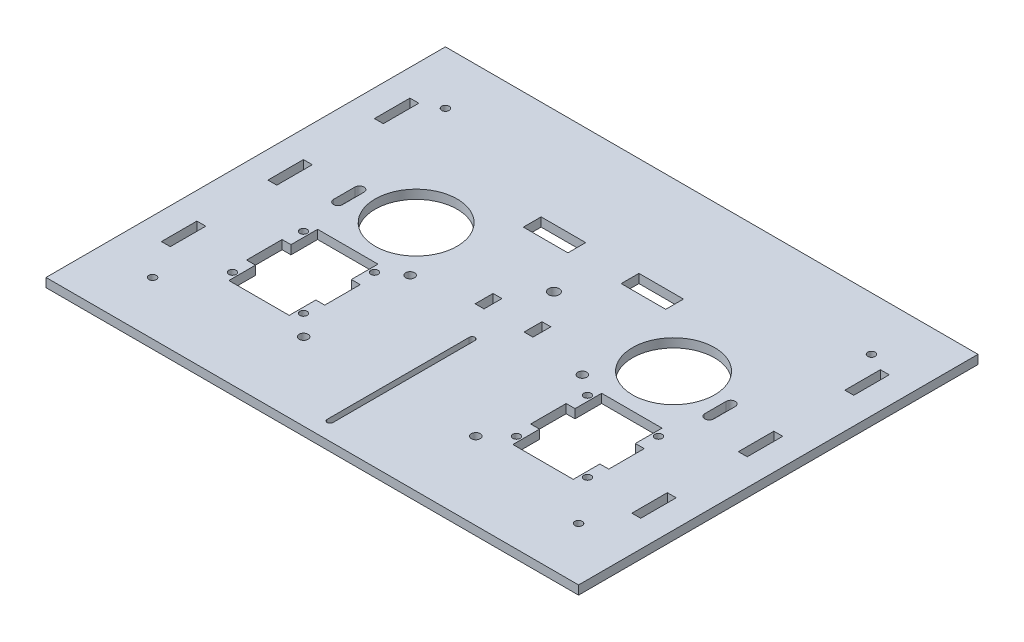
SolidWorks part; units mm, degrees
ref_plane "前基準面" through (0, 0, 0) normal (0, 0, 1) x (1, 0, 0)
ref_plane "上基準面" through (0, 0, 0) normal (0, 1, 0) x (1, 0, 0)
ref_plane "右基準面" through (0, 0, 0) normal (1, 0, 0) x (0, 0, -1)
sketch "草圖1" plane through (0, 0, 0) normal (0, 1, 0) x (1, 0, 0)
  line L0 (-130, 90) -> (130, 90) construction
  line L1 (-150, 100) -> (150, 100) construction
  line L2 (-150, 100) -> (-150, -100)
  line L3 (-150, -100) -> (150, -100) construction
  line L5 (0, 100) -> (0, -100) construction
  line L8 (-130, 100) -> (-110, 100) construction
  line L9 (-150, 100) -> (-150, -100) construction
  line L16 (-130, 100) -> (-130, -100) construction
  line L17 (-130, -100) -> (-110, -100) construction
  line L20 (-150, -100) -> (-150, -120)
  line L23 (-150, -100) -> (150, -100) construction
  line L35 (-110, 100) -> (-110, -100) construction
  line L38 (-110, 100) -> (110, 100) construction
  line L41 (-110, 100) -> (-110, 80) construction
  line L50 (-110, 80) -> (110, 80) construction
  line L59 (110, 100) -> (110, 80) construction
  line L65 (-150, -100) -> (150, -100) construction
  line L68 (150, -100) -> (150, 100)
  line L70 (-150, 100) -> (150, 100) construction
  line L73 (-150, 100) -> (-150, 105)
  line L77 (110, 100) -> (130, 100) construction
  line L80 (110, 100) -> (110, -100) construction
  line L83 (110, -100) -> (130, -100) construction
  line L86 (130, 100) -> (130, -100) construction
  line L89 (110, -100) -> (-110, -100) construction
  line L92 (110, -100) -> (110, -80) construction
  line L93 (-150, 100) -> (150, 100) construction
  line L97 (-150, 105) -> (150, 105)
  line L98 (150, 100) -> (150, 105)
  line L99 (-150, -120) -> (150, -120)
  line L100 (150, -120) -> (150, -100)
  line L108 (110, -80) -> (-110, -80) construction
  line L109 (-110, -100) -> (-110, -80) construction
  line L110 (130, -70) -> (135, -70)
  line L111 (-120, 100) -> (-120, -100) construction
  line L112 (-130, -90) -> (130, -90) construction
  line L113 (120, -100) -> (120, 100) construction
  line L114 (-130, 70) -> (-135, 70)
  line L115 (-130, 70) -> (-130, 50)
  line L116 (-130, 50) -> (-135, 50)
  line L117 (-135, 70) -> (-135, 50)
  line L118 (-130, 10) -> (-135, 10)
  line L119 (-130, 10) -> (-130, -10)
  line L120 (-130, -10) -> (-135, -10)
  line L121 (-135, 10) -> (-135, -10)
  line L122 (-130, -50) -> (-135, -50)
  line L123 (-130, -50) -> (-130, -70)
  line L124 (-130, -70) -> (-135, -70)
  line L125 (-135, -50) -> (-135, -70)
  line L126 (135, -50) -> (135, -70)
  line L127 (130, -50) -> (135, -50)
  line L128 (130, -50) -> (130, -70)
  line L129 (130, -10) -> (135, -10)
  line L130 (135, 10) -> (135, -10)
  line L131 (130, 10) -> (135, 10)
  line L132 (130, 10) -> (130, -10)
  line L133 (130, 50) -> (135, 50)
  line L134 (135, 70) -> (135, 50)
  line L135 (130, 70) -> (135, 70)
  line L136 (130, 70) -> (130, 50)
  circle A73 centre (-120, 75) radius 2.1
  circle A74 centre (120, 75) radius 2.1
  circle A75 centre (120, -90) radius 2.1
  circle A76 centre (-120, -90) radius 2.1
  point P6 (0, 0)
  point P9 (0, -80)
  point P24 (-140, 64.2857)
  point P47 (-140, 38.5714)
  point P54 (-140, 12.8571)
  point P61 (-140, -12.8571)
  point P71 (-140, -38.5714)
  point P78 (-140, -64.2857)
  dimension "D3" = 300
  dimension "D5" = 20
  dimension "D8" = 220
  dimension "D13" = 4.2
  dimension "D14" = 20
  dimension "D2" = 200
  dimension "D4" = 20
  dimension "D6" = 20
  dimension "D7" = 20
  dimension "D9" = 10
  dimension "D10" = 10
  dimension "D11" = 10
  dimension "D12" = 10
  dimension "D15" = 20
  dimension "D16" = 20
  dimension "D17" = 20
  dimension "D18" = 5
  dimension "D19" = 40
  dimension "D20" = 40
  dimension "D21" = 30
  dimension "D22" = 25
  dimension "D24" = 5
extrude "填料-伸長1" add sketch "草圖1" along normal blind 5
sketch "草圖2" plane through (0, 5, 0) normal (0, 1, 0) x (1, 0, 0)
  line L0 (0, 116.4556) -> (0, -113.9778) construction
  line L1 (115, 11) -> (30, 11) construction
  line L2 (-72.5, 53.5) -> (-72.5, -31.5) construction
  line L3 (-115, 11) -> (-30, 11) construction
  line L4 (72.5, 53.5) -> (72.5, -31.5) construction
  line L10 (7.5, -98.8861) -> (-7.5, -98.8861) construction
  line L15 (7.5, -98.8861) -> (7.5, -28.8861) construction
  line L16 (7.5, -28.8861) -> (-7.5, -28.8861) construction
  line L17 (-7.5, -98.8861) -> (-7.5, -28.8861) construction
  line L20 (-7.5, -28.8861) -> (7.5, -28.8861) construction
  line L35 (-110, 100) -> (-110, -100) construction
  line L36 (36, -91.3861) -> (-36, -91.3861) construction
  line L37 (36, -91.3861) -> (36, 18.6139) construction
  line L38 (36, 18.6139) -> (-36, 18.6139) construction
  line L39 (-36, -91.3861) -> (-36, 18.6139) construction
  line L40 (-105, -20) -> (-55, -20) construction
  line L41 (-105, -20) -> (-105, -70) construction
  line L42 (-55, -20) -> (-55, -70) construction
  line L43 (-97, -20) -> (-63, -20)
  line L46 (-97, -20) -> (-97, -70)
  line L49 (-97, -70) -> (-63, -70)
  line L60 (-7.5, -51.3861) -> (7.5, -51.3861)
  line L61 (-7.5, -51.3861) -> (-7.5, -76.3861)
  line L62 (-7.5, -76.3861) -> (7.5, -76.3861)
  line L63 (7.5, -51.3861) -> (7.5, -76.3861)
  line L64 (-63, -20) -> (-63, -70)
  line L67 (-105, -70) -> (-55, -70) construction
  line L72 (-150, 100) -> (150, 100) construction
  line L73 (-150, -100) -> (150, -100) construction
  line L74 (97, -20) -> (97, -70)
  line L75 (240, -96.3861) -> (-240, -96.3861) construction
  line L76 (240, -96.3861) -> (240, -16.3861) construction
  line L78 (-240, -96.3861) -> (-240, -16.3861) construction
  line L83 (0, -40.4951) -> (0, 39.5049) construction
  line L84 (-150, 100) -> (150, 100)
  line L85 (97, -70) -> (63, -70)
  line L86 (63, -20) -> (63, -70)
  line L87 (97, -20) -> (63, -20)
  line L88 (-7.5, -91.3861) -> (-7.5, -116.3861)
  line L89 (-7.5, -91.3861) -> (7.5, -91.3861)
  line L90 (7.5, -91.3861) -> (7.5, -116.3861)
  line L91 (-7.5, -116.3861) -> (7.5, -116.3861)
  line L92 (240, -16.3861) -> (-240, -16.3861) construction
  circle A0 centre (-72.5, 11) radius 42.5
  circle A1 centre (-72.5, 11) radius 22.1
  circle A2 centre (-87, 11) radius 2
  circle A3 centre (-58, 11) radius 2
  circle A4 centre (58, 11) radius 2
  circle A5 centre (87, 11) radius 2
  circle A6 centre (72.5, 11) radius 22.1
  circle A7 centre (72.5, 11) radius 42.5
  circle A11 centre (0, -86.3861) radius 1.25 construction
  circle A12 centre (0, -16.3861) radius 35 construction
  circle A13 centre (0, -41.3861) radius 1.25 construction
  circle A28 centre (60, -65) radius 2.05
  circle A36 centre (-100, -25) radius 2.05
  circle A37 centre (-60, -25) radius 2.05
  circle A38 centre (-100, -65) radius 2.05
  circle A39 centre (-60, -65) radius 2.05
  circle A40 centre (100, -65) radius 2.05
  circle A41 centre (60, -25) radius 2.05
  circle A42 centre (100, -25) radius 2.05
  circle A43 centre (0, -56.3861) radius 35 construction
  point P29 (0, 18.6139)
  point P46 (-7.5, -63.8861)
  point P57 (-7.5, -63.8861)
  point P85 (-96.5, 66.7857)
  point P90 (-141.5, 66.7857)
  point P91 (-140, 13.2857)
  point P92 (-140, 68.2857)
  point P116 (0, -98.8861)
  point P142 (0, -96.3861)
  point P143 (0, 53.9014)
  dimension "D1" = 85
  dimension "D2" = 44.2
  dimension "D4" = 4
  dimension "D8" = 72
  dimension "D10" = 89
  dimension "D7" = 2
  dimension "D16" = 70
  dimension "D13" = 2.5
  dimension "D17" = 2
  dimension "D24" = 45
  dimension "D25" = 4.1
  dimension "D33" = 8
  dimension "D3" = 29
  dimension "D5" = 60
  dimension "D6" = 12.5
  dimension "D9" = 25
  dimension "D11" = 70
  dimension "D12" = 110
  dimension "D14" = 5
  dimension "D15" = 5
  dimension "D18" = 40
  dimension "D19" = 40
  dimension "D20" = 45
  dimension "D21" = 34
  dimension "D23" = 30
  dimension "D26" = 2
  dimension "D27" = 40
  dimension "D29" = 55
  dimension "D30" = 50
  dimension "D31" = 15
  dimension "D32" = 40
  dimension "D40" = 5
  dimension "D41" = 5
  dimension "D42" = 50
  dimension "D43" = 80
  dimension "D44" = 480
sketch "草圖3" plane through (0, 5, 0) normal (0, 1, 0) x (1, 0, 0)
  line L0 (0, 200116.4556) -> (0, -200113.9778) construction
  line L1 (0, 200116.4556) -> (0, -200113.9778) construction
  line L2 (0, 100) -> (0, -100) construction
  line L3 (-41, -6.3861) -> (-56, -6.3861) construction
  line L4 (-41, -6.3861) -> (-41, -26.3861) construction
  line L5 (-41, -26.3861) -> (-56, -26.3861) construction
  line L6 (-56, -6.3861) -> (-56, -26.3861) construction
  line L7 (0, 0) -> (0, 42.1207) construction
  line L8 (41, -26.3861) -> (56, -26.3861) construction
  line L9 (-7.5, -98.8861) -> (-7.5, -28.8861) construction
  line L10 (7.5, -28.8861) -> (-7.5, -28.8861) construction
  line L11 (7.5, -28.8861) -> (7.5, -18.8861) construction
  line L12 (7.5, -18.8861) -> (-7.5, -18.8861) construction
  line L13 (-7.5, -28.8861) -> (-7.5, -18.8861) construction
  line L14 (41, -6.3861) -> (41, -26.3861) construction
  line L15 (56, -6.3861) -> (56, -26.3861) construction
  line L16 (41, -6.3861) -> (56, -6.3861) construction
  line L17 (-97, -70) -> (-63, -70) construction
  line L18 (-63, -20) -> (-63, -70) construction
  line L19 (-97, -20) -> (-63, -20) construction
  line L20 (-97, -20) -> (-97, -70) construction
  line L21 (-97, -70) -> (-63, -70)
  line L22 (-63, -20) -> (-63, -35)
  line L23 (-97, -20) -> (-63, -20)
  line L24 (-97, -20) -> (-97, -35)
  line L25 (97, -20) -> (97, -35)
  line L26 (97, -20) -> (63, -20)
  line L27 (63, -20) -> (63, -35)
  line L28 (97, -70) -> (63, -70)
  line L29 (36, 18.6139) -> (-36, 18.6139) construction
  line L30 (-11.275, 23.1139) -> (11.275, 23.1139) construction
  line L31 (-11.275, 23.1139) -> (-11.275, -13.8861) construction
  line L32 (-11.275, -13.8861) -> (11.275, -13.8861) construction
  line L33 (11.275, 23.1139) -> (11.275, -13.8861) construction
  line L34 (-11.275, -1.8861) -> (-16.275, -1.8861)
  line L35 (-11.275, -1.8861) -> (-11.275, -11.9861)
  line L36 (-11.275, -11.9861) -> (-16.275, -11.9861)
  line L37 (-16.275, -1.8861) -> (-16.275, -11.9861)
  line L38 (11.275, -1.8861) -> (16.275, -1.8861)
  line L39 (11.275, -1.8861) -> (11.275, -11.9861)
  line L40 (11.275, -11.9861) -> (16.275, -11.9861)
  line L41 (16.275, -1.8861) -> (16.275, -11.9861)
  line L42 (-1.6, -70) -> (1.6, -70) construction
  line L43 (0, -30) -> (0, -110) construction
  line L44 (1.6, -30) -> (1.6, -110)
  line L45 (-1.6, -30) -> (-1.6, -110)
  line L46 (63, -55) -> (58, -55)
  line L47 (-97, -35) -> (-102, -35)
  line L49 (-97, -55) -> (-102, -55)
  line L50 (-102, -35) -> (-102, -55)
  line L51 (-63, -35) -> (-58, -35)
  line L53 (-63, -55) -> (-58, -55)
  line L54 (-58, -35) -> (-58, -55)
  line L55 (58, -35) -> (58, -55)
  line L56 (63, -35) -> (58, -35)
  line L58 (97, -55) -> (102, -55)
  line L59 (102, -35) -> (102, -55)
  line L60 (97, -35) -> (102, -35)
  line L62 (-97, -55) -> (-97, -70)
  line L63 (-63, -55) -> (-63, -70)
  line L64 (63, -55) -> (63, -70)
  line L65 (97, -55) -> (97, -70)
  line L66 (-80, -20) -> (-80, -70) construction
  line L68 (-150, -120) -> (150, -120) construction
  arc A0 (1.6, -30) -> (-1.6, -30) centre (0, -30) ccw
  arc A2 (-1.6, -110) -> (1.6, -110) centre (0, -110) ccw
  circle A4 centre (120, -90) radius 2.1 construction
  circle A6 centre (120, -90) radius 2.1 construction
  circle A10 centre (-48.5, -16.3861) radius 2.5
  circle A11 centre (48.5, -16.3861) radius 2.5
  circle A12 centre (48.5, -76.3861) radius 2.5
  circle A13 centre (-48.5, -76.3861) radius 2.5
  circle A14 centre (-72.5, 11) radius 22.1 construction
  circle A15 centre (-72.5, 11) radius 22.1 construction
  circle A16 centre (72.5, 11) radius 22.1 construction
  circle A17 centre (72.5, 11) radius 22.1 construction
  circle A18 centre (-72.5, 11) radius 23.1
  circle A19 centre (72.5, 11) radius 23.1
  circle A20 centre (0, 16.1139) radius 3
  circle A21 centre (0, -23.8861) radius 2 construction
  circle A22 centre (-100, -65) radius 2.05 construction
  circle A23 centre (-60, -65) radius 2.05 construction
  circle A24 centre (-60, -25) radius 2.05 construction
  circle A25 centre (-100, -25) radius 2.05 construction
  circle A26 centre (-100, -65) radius 2.05
  circle A27 centre (-60, -65) radius 2.05
  circle A28 centre (-60, -25) radius 2.05
  circle A29 centre (-100, -25) radius 2.05
  circle A30 centre (100, -25) radius 2.05
  circle A31 centre (60, -25) radius 2.05
  circle A32 centre (60, -65) radius 2.05
  circle A33 centre (100, -65) radius 2.05
  circle A34 centre (0, -106.6) radius 1.6 construction
  circle A35 centre (0, -33.4) radius 1.6 construction
  point P1 (0, -70)
  point P29 (-56, -16.3861)
  point P32 (-48.5, -26.3861)
  point P62 (-7.5, -23.8861)
  point P64 (0, 23.1139)
  point P107 (-102, -45)
  point P120 (-80, -45)
  dimension "D2" = 5
  dimension "D8" = 6
  dimension "D11" = 4
  dimension "D7" = 1
  dimension "D20" = 1
  dimension "D21" = 5
  dimension "D26" = 50
  dimension "D3" = 15
  dimension "D4" = 20
  dimension "D5" = 2
  dimension "D6" = 60
  dimension "D9" = 40
  dimension "D10" = 10
  dimension "D12" = 112
  dimension "D13" = 25
  dimension "D14" = 22.55
  dimension "D15" = 37
  dimension "D16" = 7
  dimension "D17" = 5
  dimension "D18" = 10.1
  dimension "D19" = 25
  dimension "D22" = 3.2
  dimension "D23" = 20
  dimension "D24" = 80
  dimension "D25" = 73.2
extrude "除料-伸長1" cut sketch "草圖3" against normal through all
sketch "草圖5" plane through (0, 5, 0) normal (0, 1, 0) x (1, 0, 0)
  line L0 (-150, 39) -> (150, 39) construction
  line L1 (-150, 105) -> (-150, -120) construction
  line L2 (150, -120) -> (150, 105) construction
  line L3 (-144.2587, 49) -> (142.9694, 49) construction
  line L4 (-150, 100) -> (-150, 105) construction
  line L5 (0, 36.1139) -> (0, 16.1139) construction
  line L8 (-0.85, 16.1139) -> (0.85, 16.1139) construction
  line L9 (-0.85, 18.0139) -> (0.85, 18.0139) construction
  line L10 (-0.85, 14.2139) -> (0.85, 14.2139) construction
  line L11 (5.05, 36.1139) -> (5.05, 16.1139) construction
  line L12 (-5.05, 36.1139) -> (-5.05, 16.1139) construction
  line L13 (0, 0) -> (0, 152.3042) construction
  line L14 (-15, 49) -> (15, 49) construction
  line L15 (-15, 49) -> (-15, 39) construction
  line L16 (-15, 39) -> (15, 39) construction
  line L17 (15, 49) -> (15, 39) construction
  line L18 (15, 39) -> (40.1, 39)
  line L19 (-15, 49) -> (-40.1, 49)
  line L20 (-15, 49) -> (-15, 39)
  line L21 (-15, 39) -> (-40.1, 39)
  line L22 (-40.1, 49) -> (-40.1, 39)
  line L23 (40.1, 49) -> (40.1, 39)
  line L24 (15, 49) -> (40.1, 49)
  line L25 (15, 49) -> (15, 39)
  line L26 (-150, 100) -> (150, 100) construction
  line L27 (-150, 100) -> (150, 100) construction
  line L28 (-104.55, 11.15) -> (-104.55, -0.95) construction
  line L31 (-102, 11.15) -> (-102, -0.95)
  line L32 (-130, 70) -> (-110, 70) construction
  line L33 (-130, 70) -> (-130, 30.1754) construction
  line L34 (-130, 30.1754) -> (-110, 30.1754) construction
  line L35 (-110, 70) -> (-110, 30.1754) construction
  line L36 (0, 100) -> (0, -100) construction
  line L39 (-98.5, 39) -> (-46.5, 39) construction
  line L40 (-98.5, 39) -> (-98.5, 37) construction
  line L41 (-98.5, 37) -> (-46.5, 37) construction
  line L42 (-46.5, 39) -> (-46.5, 37) construction
  line L43 (-111.8, 63.9563) -> (-99.5, 63.9563) construction
  line L44 (-111.8, 63.9563) -> (-111.8, -8.5) construction
  line L45 (-111.8, -8.5) -> (-99.5, -8.5) construction
  line L46 (-99.5, 63.9563) -> (-99.5, -8.5) construction
  line L47 (-107.1, 11.15) -> (-107.1, -0.95)
  line L48 (104.55, 11.15) -> (104.55, -0.95) construction
  line L49 (102, 11.15) -> (102, -0.95)
  line L50 (107.1, 11.15) -> (107.1, -0.95)
  circle A0 centre (0, 16.1139) radius 3 construction
  circle A1 centre (0, 16.1139) radius 3 construction
  circle A4 centre (0, 36.1139) radius 2.05 construction
  arc A5 (-0.85, 18.0139) -> (-0.85, 14.2139) centre (-0.85, 16.1139) ccw construction
  arc A6 (0.85, 14.2139) -> (0.85, 18.0139) centre (0.85, 16.1139) ccw construction
  arc A7 (5.05, 36.1139) -> (-5.05, 36.1139) centre (0, 36.1139) ccw construction
  arc A8 (-5.05, 16.1139) -> (5.05, 16.1139) centre (0, 16.1139) ccw construction
  arc A13 (-102, 11.15) -> (-107.1, 11.15) centre (-104.55, 11.15) ccw
  arc A14 (-107.1, -0.95) -> (-102, -0.95) centre (-104.55, -0.95) ccw
  arc A15 (-107.1, 11.15) -> (-102, 11.15) centre (-104.55, 11.15) ccw construction
  arc A16 (-102, -0.95) -> (-107.1, -0.95) centre (-104.55, -0.95) ccw construction
  arc A17 (102, 11.15) -> (107.1, 11.15) centre (104.55, 11.15) cw
  arc A18 (107.1, -0.95) -> (102, -0.95) centre (104.55, -0.95) cw
  point P3 (0, 26.1139)
  point P18 (0, 11.0639)
  point P19 (0, 41.1639)
  point P24 (0, 16.1139)
  point P29 (-2.75, 16.1139)
  point P30 (2.75, 16.1139)
  point P38 (0, 49)
  point P46 (-104.55, 5.1)
  point P51 (-104.55, -3.5)
  point P57 (-105.65, 66.45)
  point P79 (-104.55, 1.6)
  point P80 (-104.55, 8.6)
  point P84 (104.55, 5.1)
  dimension "D1" = 20
  dimension "D2" = 4.1
  dimension "D12" = 5.1
  dimension "D19" = 7
  dimension "D3" = 10
  dimension "D4" = 61
  dimension "D5" = 30.1
  dimension "D6" = 5.5
  dimension "D7" = 3.8
  dimension "D8" = 30
  dimension "D9" = 25.1
  dimension "D10" = 5
  dimension "D11" = 2.5
  dimension "D13" = 20
  dimension "D14" = 1
  dimension "D15" = 12.3
  dimension "D16" = 52
  dimension "D17" = 51.5
  dimension "D18" = 2
  dimension "D20" = 47.5
  dimension "D21" = 12.1
extrude "除料-伸長5" cut sketch "草圖5" against normal through all
